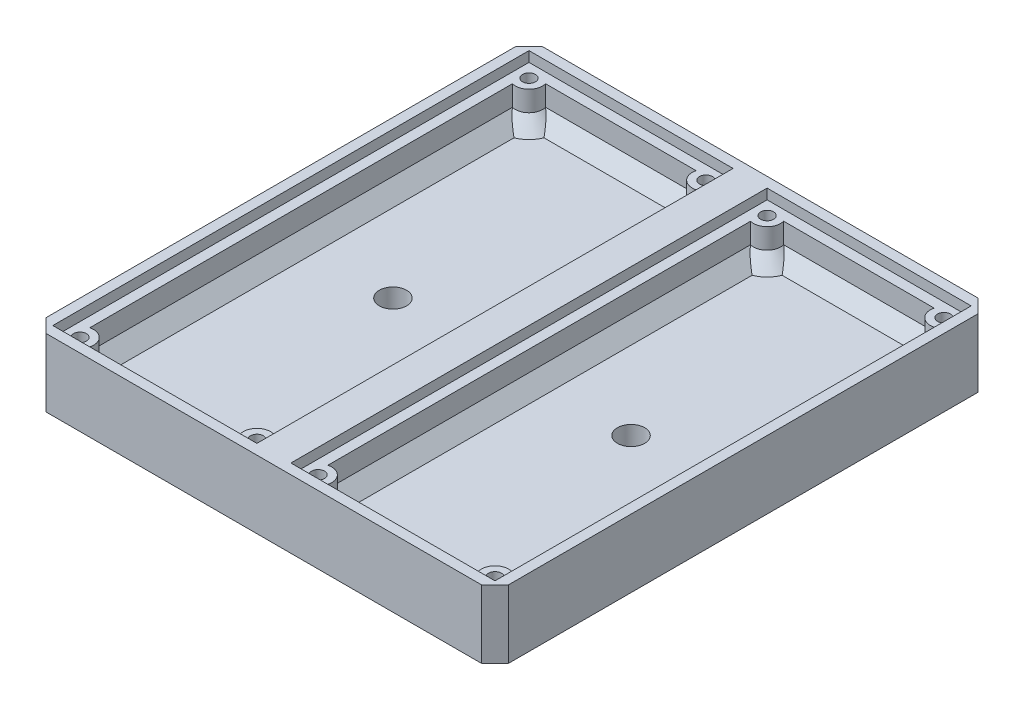
SolidWorks part; units mm, degrees
ref_plane "Front Plane" through (0, 0, 0) normal (0, 0, 1) x (1, 0, 0)
ref_plane "Top Plane" through (0, 0, 0) normal (0, 1, 0) x (1, 0, 0)
ref_plane "Right Plane" through (0, 0, 0) normal (1, 0, 0) x (0, 0, -1)
sketch "Sketch2" plane through (0, 0, 0) normal (0, 1, 0) x (1, 0, 0)
  line L1 (-34, -36.5) -> (34, -36.5)
  line L2 (-34, -36.5) -> (-34, 36.5)
  line L3 (-34, 36.5) -> (34, 36.5)
  line L4 (34, -36.5) -> (34, 36.5)
  line L5 (-34, -36.5) -> (34, 36.5) construction
  line L6 (-34, 36.5) -> (34, -36.5) construction
  line L7 (-32.5, -35) -> (-2.5, -35)
  line L8 (-32.5, -35) -> (-32.5, 35)
  line L9 (-32.5, 35) -> (-2.5, 35)
  line L10 (-2.5, -35) -> (-2.5, 35)
  line L11 (-32.5, -35) -> (-2.5, 35) construction
  line L12 (-32.5, 35) -> (-2.5, -35) construction
  line L13 (2.5, -35) -> (32.5, -35)
  line L14 (2.5, -35) -> (2.5, 35)
  line L15 (2.5, 35) -> (32.5, 35)
  line L16 (32.5, -35) -> (32.5, 35)
  line L17 (2.5, -35) -> (32.5, 35) construction
  line L18 (2.5, 35) -> (32.5, -35) construction
  point P0 (0, 0)
  point P6 (-17.5, 0)
  point P11 (17.5, 0)
  dimension "D1" = 68
  dimension "D2" = 30
  dimension "D3" = 30
  dimension "D4" = 1.5
  dimension "D5" = 1.5
  dimension "D6" = 1.5
  dimension "D7" = 70
  dimension "D8" = 1.5
extrude "Boss-Extrude1" add sketch "Sketch2" against normal blind 10 contours L7 L10 L9 L8 | L13 L16 L15 L14 | L1 L4 L3 L2 L16 L13 L14 L15 L10 L7 L8 L9 | L2 L1 L4 L3 region at (0, 0, 0) region at (-17.5, 0, 0) region at (17.5, 0, 0)
extrude "Cut-Extrude2" cut sketch "Sketch2<3>" against normal blind 1.5 contours L7 L10 L9 L8 | L13 L16 L15 L14 region at (-17.5, 0, 0) region at (17.5, 0, 0)
sketch "Sketch2<3>" plane through (0, 0, 0) normal (0, 1, 0) x (1, 0, 0) same geometry as "Sketch2"
sketch "Sketch3" plane through (0, -1.5, 0) normal (0, 1, 0) x (1, 0, 0)
  line L8 (-31, -33.5) -> (-4, -33.5)
  line L9 (-4, -33.5) -> (-4, 33.5)
  line L10 (-4, 33.5) -> (-31, 33.5)
  line L11 (-31, 33.5) -> (-31, -33.5)
  line L12 (-31, -33.5) -> (-4, -33.5)
  line L13 (-4, -33.5) -> (-4, 33.5)
  line L14 (-4, 33.5) -> (-31, 33.5)
  line L15 (-31, 33.5) -> (-31, -33.5)
  line L20 (4, -33.5) -> (31, -33.5)
  line L21 (31, -33.5) -> (31, 33.5)
  line L22 (31, 33.5) -> (4, 33.5)
  line L23 (4, 33.5) -> (4, -33.5)
  line L24 (4, -33.5) -> (31, -33.5)
  line L25 (31, -33.5) -> (31, 33.5)
  line L26 (31, 33.5) -> (4, 33.5)
  line L27 (4, 33.5) -> (4, -33.5)
  dimension "D1" = 1.5
  dimension "D2" = 1.5
extrude "Cut-Extrude3" cut sketch "Sketch3" against normal blind 5
sketch "Sketch4" plane through (0, -6.5, 0) normal (0, 1, 0) x (1, 0, 0)
  line L0 (-4, 33.5) -> (-31, 33.5) construction
  line L1 (-4.5, -33) -> (-30.5, -33) construction
  line L2 (-4.5, -33) -> (-4.5, 33) construction
  line L3 (-4.5, 33) -> (-30.5, 33) construction
  line L4 (-30.5, -33) -> (-30.5, 33) construction
  line L5 (-4.5, -33) -> (-30.5, 33) construction
  line L6 (-4.5, 33) -> (-30.5, -33) construction
  line L7 (0, -55) -> (0, 55) construction
  line L8 (4.5, 33) -> (30.5, -33) construction
  line L9 (4.5, -33) -> (30.5, 33) construction
  line L10 (30.5, -33) -> (30.5, 33) construction
  line L11 (4.5, 33) -> (30.5, 33) construction
  line L12 (4.5, -33) -> (4.5, 33) construction
  line L13 (4.5, -33) -> (30.5, -33) construction
  circle A0 centre (-30.5, 33) radius 2
  circle A1 centre (-4.5, 33) radius 2
  circle A2 centre (-4.5, -33) radius 2
  circle A3 centre (-30.5, -33) radius 2
  circle A4 centre (30.5, -33) radius 2
  circle A5 centre (4.5, -33) radius 2
  circle A6 centre (4.5, 33) radius 2
  circle A7 centre (30.5, 33) radius 2
  point P0 (-17.5, 0)
  point P7 (-17.5, 33.5)
  point P24 (17.5, 0)
  dimension "D3" = 4
  dimension "D1" = 26
  dimension "D2" = 66
  dimension "D4" = 2
  dimension "D5" = 2
extrude "Boss-Extrude2" add sketch "Sketch4" along normal up to surface (5 mm away) up to face at (-17.5, -1.5, 0)
sketch "Sketch5" plane through (0, -1.5, 0) normal (0, 1, 0) x (1, 0, 0)
  line L0 (-30.5, 33) -> (-4.5, 33) construction
  line L1 (-30.5, 33) -> (-30.5, -33) construction
  line L2 (0, -55) -> (0, 55) construction
  line L3 (30.5, 33) -> (30.5, -33) construction
  line L4 (30.5, 33) -> (4.5, 33) construction
  circle A0 centre (-30.5, 33) radius 0.95
  circle A1 centre (-4.5, 33) radius 0.95
  circle A2 centre (-4.5, -33) radius 0.95
  circle A3 centre (-30.5, -33) radius 0.95
  circle A4 centre (30.5, -33) radius 0.95
  circle A5 centre (4.5, -33) radius 0.95
  circle A6 centre (4.5, 33) radius 0.95
  circle A7 centre (30.5, 33) radius 0.95
  dimension "D1" = 1.9
  dimension "D4" = 26
  dimension "D5" = 66
  dimension "D2" = 2
  dimension "D3" = 2
extrude "Cut-Extrude4" cut sketch "Sketch5" along normal up to surface (1.5 mm away) and the other way up to surface (5 mm away) up to face at (-17.5, 0, 0) other way up to face at (-17.5, -6.5, 0)
chamfer "Chamfer1" distance 2 angle 45 4 edges at (34, -5, -36.5) (-34, -5, -36.5) (34, -5, 36.5) (-34, -5, 36.5)
chamfer "Chamfer2" distance 2 angle 45 16 edges at (29.0858, -6.5, 31.5858) (17.5, -6.5, 33.5) (5.9142, -6.5, 31.5858) (4, -6.5, 0) (5.9142, -6.5, -31.5858) (17.5, -6.5, -33.5) (29.0858, -6.5, -31.5858) (31, -6.5, 0) (-29.0858, -6.5, -31.5858) (-17.5, -6.5, -33.5) (-5.9142, -6.5, -31.5858) (-4, -6.5, 0) (-5.9142, -6.5, 31.5858) (-17.5, -6.5, 33.5) (-29.0858, -6.5, 31.5858) (-31, -6.5, 0)
sketch "Sketch6" plane through (0, -10, 0) normal (0, -1, 0) x (1, 0, 0)
  line L0 (-28.5635, -33.5) -> (-6.4365, -33.5) construction
  line L1 (28.5635, -33.5) -> (6.4365, -33.5) construction
  circle A0 centre (-17.5, 0) radius 2
  circle A1 centre (17.5, 0) radius 2
  point P6 (-17.5, -33.5)
  point P9 (17.5, -33.5)
  dimension "D1" = 4
  dimension "D2" = 4
extrude "Cut-Extrude5" cut sketch "Sketch6" against normal blind 4
